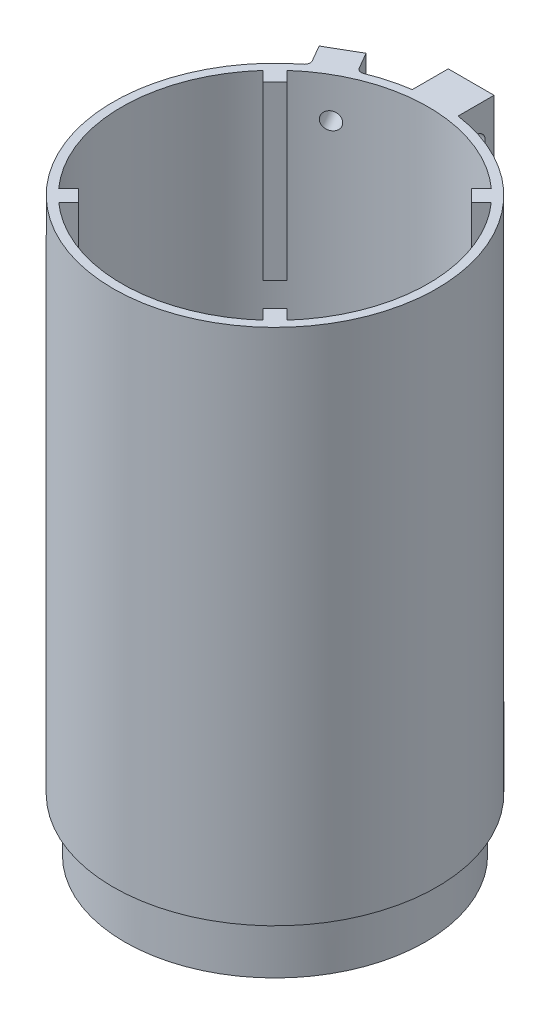
SolidWorks part; units mm, degrees
ref_plane "Ebene vorne" through (0, 0, 0) normal (0, 0, 1) x (1, 0, 0)
ref_plane "Ebene oben" through (0, 0, 0) normal (0, 1, 0) x (1, 0, 0)
ref_plane "Ebene rechts" through (0, 0, 0) normal (1, 0, 0) x (0, 0, -1)
sketch "Skizze1" plane through (0, 0, 0) normal (0, 1, 0) x (1, 0, 0)
  circle A0 centre (0, 0) radius 25.75
  circle A1 centre (0, 0) radius 26.25
  dimension "D1" = 51.5
  dimension "D2" = 0.5
extrude "Aufsatz-Linear austragen1" add sketch "Skizze1" along normal blind 9.8
sketch "Skizze2" plane through (0, 9.8, 0) normal (0, 1, 0) x (1, 0, 0)
  circle A0 centre (0, 0) radius 25.75 construction
  circle A1 centre (0, 0) radius 26.75
  circle A4 centre (0, 0) radius 25.75 construction
  circle A5 centre (0, 0) radius 28.25
  dimension "D1" = 53.5
  dimension "D2" = 1.5
extrude "Aufsatz-Linear austragen2" add sketch "Skizze2" along normal blind 90
sketch "Skizze4" plane through (0, 99.8, 0) normal (0, 1, 0) x (1, 0, 0)
  line L0 (0, 0) -> (0, 39.3714) construction
  line L1 (-4, 27.1581) -> (4, 27.1581)
  line L2 (4, 27.1581) -> (4, 34.25)
  line L3 (4, 34.25) -> (-4, 34.25)
  line L4 (0, 28.25) -> (10.2613, 28.25) construction
  line L5 (-4, 27.1581) -> (-4, 34.25)
  circle A0 centre (0, 0) radius 28.25 construction
  point P12 (0, 34.25)
  point P13 (0, 27.1581)
  dimension "D1" = 8
  dimension "D2" = 6
extrude "Aufsatz-Linear austragen4" add sketch "Skizze4" against normal blind 10
sketch "Skizze5" plane through (0, 9.8, 0) normal (0, -1, 0) x (1, 0, 0)
  circle A0 centre (0, 0) radius 28.25
  circle A1 centre (0, 0) radius 28.25 construction
  circle A2 centre (0, 0) radius 25.25
  circle A3 centre (0, 0) radius 25.75 construction
  dimension "D1" = 0.5
extrude "Aufsatz-Linear austragen5" add sketch "Skizze5" along normal blind 0.5
sketch "Skizze6" plane through (-4, 0, 0) normal (-1, 0, 0) x (0, 0, 1)
  line L0 (-31.1077, 99.8) -> (-31.1077, 89.8) construction
  line L1 (-34.25, 99.8) -> (-27.9654, 99.8) construction
  line L2 (-34.25, 89.8) -> (-27.9654, 89.8) construction
  circle A0 centre (-31.1077, 93.8) radius 1.6
  dimension "D1" = 3.2
  dimension "D2" = 6
extrude "Schnitt-Linear austragen1" cut sketch "Skizze6" against normal through all
sketch "Skizze7" plane through (0, 99.8, 0) normal (0, 1, 0) x (1, 0, 0)
  line L0 (0, 0) -> (0, 39.9199) construction
  line L1 (0, 0) -> (-24.7065, 24.7065) construction
  line L2 (0, 0) -> (23.5714, 23.5714) construction
  line L3 (-17.8247, 19.946) -> (-16.0867, 18.208)
  line L4 (-16.0867, 18.208) -> (-18.208, 16.0867)
  line L5 (-18.9151, 18.9151) -> (-16.4061, 21.4241) construction
  line L6 (-19.946, 17.8247) -> (-18.208, 16.0867)
  line L7 (-19.946, 17.8247) -> (-19.4383, 19.4383)
  line L8 (-19.4383, 19.4383) -> (-17.8247, 19.946)
  line L9 (19.4383, 19.4383) -> (17.8247, 19.946)
  line L10 (19.946, 17.8247) -> (19.4383, 19.4383)
  line L11 (19.946, 17.8247) -> (18.208, 16.0867)
  line L12 (16.0867, 18.208) -> (18.208, 16.0867)
  line L13 (17.8247, 19.946) -> (16.0867, 18.208)
  line L14 (0, 0) -> (17.578, 0) construction
  line L15 (17.8247, -19.946) -> (16.0867, -18.208)
  line L16 (16.0867, -18.208) -> (18.208, -16.0867)
  line L17 (19.946, -17.8247) -> (18.208, -16.0867)
  line L18 (19.946, -17.8247) -> (19.4383, -19.4383)
  line L19 (19.4383, -19.4383) -> (17.8247, -19.946)
  line L20 (-19.4383, -19.4383) -> (-17.8247, -19.946)
  line L21 (-19.946, -17.8247) -> (-19.4383, -19.4383)
  line L22 (-19.946, -17.8247) -> (-18.208, -16.0867)
  line L23 (-16.0867, -18.208) -> (-18.208, -16.0867)
  line L24 (-17.8247, -19.946) -> (-16.0867, -18.208)
  circle A0 centre (0, 0) radius 26.75 construction
  point P14 (-17.1473, 17.1473)
  point P20 (17.1473, 17.1473)
  point P27 (17.1473, -17.1473)
  point P33 (-17.1473, -17.1473)
  dimension "D1" = 45
  dimension "D2" = 1.5
  dimension "D3" = 2.5
extrude "Aufsatz-Linear austragen6" add sketch "Skizze7" against normal blind 30
chamfer "Fase1" distance 2 angle 45 1 edges at (0, 9.8, 26.75)
chamfer "Fase2" distance 6.5 angle 45 1 edges at (0, 89.8, -28.25)
ref_plane "Ebene1" through (-14.125, 0, -24.4652) normal (-0.5, 0, -0.866) x (0, 1, 0)
sketch "Skizze9" plane through (-14.125, 0, -24.4652) normal (-0.5, 0, -0.866) x (0, 1, 0)
  line L0 (0, 0) -> (99.8, 0) construction
  line L1 (0, 26.25) -> (0, -26.25) construction
  line L2 (99.8, -28.25) -> (99.8, 28.25) construction
  circle A0 centre (92.8, 0) radius 1.5
  circle A1 centre (92.8, 0) radius 2.75 construction
  dimension "D1" = 3
  dimension "D3" = 5.5
  dimension "D2" = 7
extrude "Schnitt-Linear austragen3" cut sketch "Skizze9" against normal blind 10
sketch "Skizze11" plane through (-14.125, 0, -24.4652) normal (-0.5, 0, -0.866) x (0, 1, 0)
  line L0 (95.8, 3) -> (99.8, 3)
  line L1 (89.8, -3) -> (95.8, -3)
  line L2 (89.8, -3) -> (89.8, 3)
  line L3 (89.8, 3) -> (95.8, 3)
  line L4 (95.8, -3) -> (95.8, 3) construction
  line L5 (89.8, -3) -> (95.8, 3) construction
  line L6 (89.8, 3) -> (95.8, -3) construction
  line L7 (99.8, -28.25) -> (99.8, 28.25) construction
  line L8 (99.8, 3) -> (99.8, -3)
  line L9 (99.8, -3) -> (95.8, -3)
  point P0 (92.8, 0)
  dimension "D1" = 6
extrude "Aufsatz-Linear austragen7" add sketch "Skizze11" along normal blind 4 and the other way blind 1
sketch "Skizze12" plane through (-16.125, 0, -27.9293) normal (-0.5, 0, -0.866) x (-0.866, 0, 0.5)
  circle A0 centre (0, 92.8) radius 1.5
  circle A3 centre (0, 92.8) radius 1.5 construction
extrude "Schnitt-Linear austragen4" cut sketch "Skizze12" against normal blind 10
fillet "Verrundung1" radius 1 2 edges at (-12.487, 89.8, -27.6281) (-17.6831, 89.8, -24.6281)
fillet "Verrundung2" radius 1 5 edges at (-16.6432, 95.3, -22.8269) (-16.4663, 90.1777, -22.9548) (-11.4471, 95.3, -25.8269) (-11.7895, 90.0203, -25.6723) (-14.125, 89.8, -24.4652)
